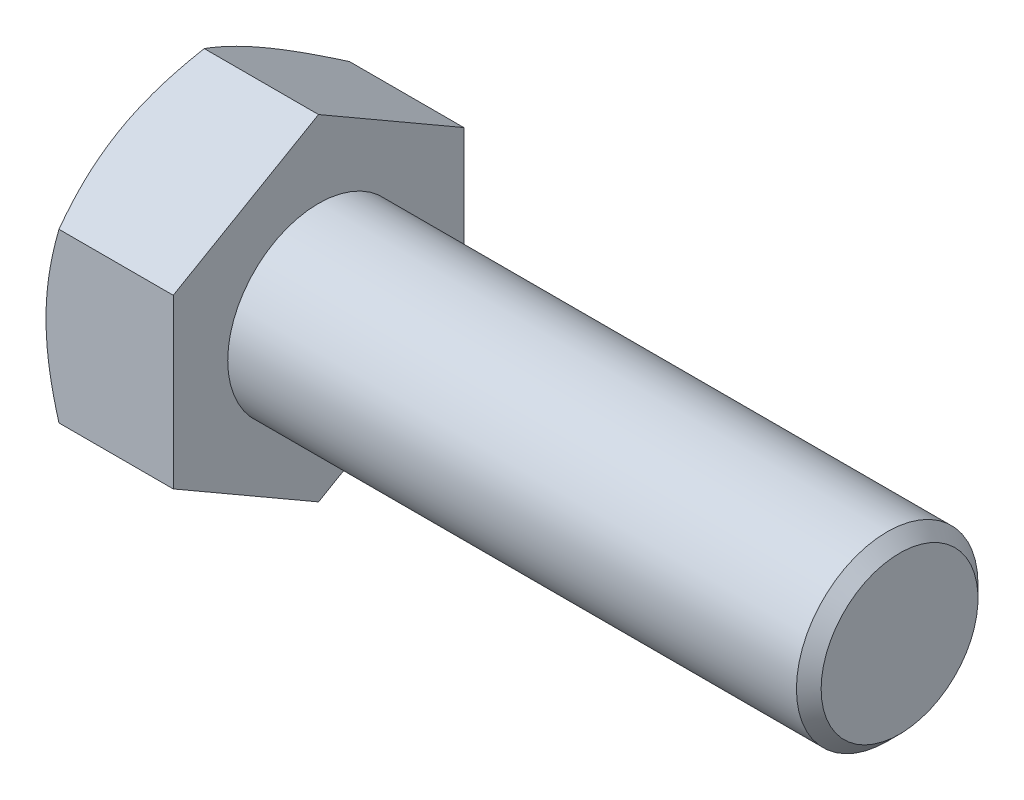
SolidWorks part; units mm, degrees
extrude "BaseHead" add sketch "Sketch1" along normal blind 22.2504
sketch "Sketch1" plane through (0, 0, 0) normal (1, 0, 0) x (0, 0, -1)
  line L0 (25.4, 14.6647) -> (25.4, -14.6647)
  line L1 (-25.4, 14.6647) -> (-25.4, -14.6647)
  line L2 (25.4, -14.6647) -> (0, -29.3294)
  line L3 (0, -29.3294) -> (-25.4, -14.6647)
  line L4 (25.4, 14.6647) -> (0, 29.3294)
  line L5 (0, 29.3294) -> (-25.4, 14.6647)
  dimension "D2" = 120
  dimension "D3" = 25.4
  dimension "D4" = 25.4
  dimension "D5" = 25.4
ref_plane "Plane1" through (0, 0, 0) normal (0, 0, 1) x (1, 0, 0)
ref_plane "Plane2" through (0, 0, 0) normal (0, 1, 0) x (1, 0, 0)
ref_plane "Plane3" through (0, 0, 0) normal (1, 0, 0) x (0, 0, -1)
sketch "BodySke" plane through (0, 0, 0) normal (0, 0, 1) x (1, 0, 0)
  line L0 (0, 14.6647) -> (0, -14.6647) construction
  line L1 (0, 0) -> (123.8504, 0)
  line L2 (0, 0) -> (0, 15.875)
  line L3 (0, 15.875) -> (121.6901, 15.875)
  line L4 (123.8504, 0) -> (123.8504, 13.7147)
  line L5 (22.2504, 29.3294) -> (22.2504, 14.6647) construction
  line L6 (123.8504, 13.7147) -> (121.6901, 15.875)
  line L7 (0, 0) -> (96.52, 0) construction
  line L8 (123.8504, -13.7147) -> (121.6901, -15.875) construction
  line L9 (0, -15.875) -> (121.6901, -15.875) construction
  line L10 (25.8801, 15.24) -> (25.8801, -3.81) construction
  line L11 (22.2504, 15.24) -> (22.2504, -3.81) construction
  line L12 (22.2504, 14.6647) -> (22.2504, -14.6647) construction
  dimension "Diameter" = 31.75
revolve "BaseBody" add sketch "BodySke" angle 360 about L7
cosmetic thread "ThreadCosmetic" [suppressed] parameters "Thread_length"=97.9703, "Thread_minor"=27.4295
sketch "Sketch3" plane through (0, 0, 0) normal (0, 0, 1) x (1, 0, 0)
  line L0 (0, 25.4) -> (5.9348, 35.6794)
  line L1 (0, 29.3294) -> (0, 14.6647) construction
  line L2 (5.9348, 35.6794) -> (5.9348, 42.0294)
  line L3 (5.9348, 42.0294) -> (-12.7, 42.0294)
  line L4 (-12.7, 42.0294) -> (-12.7, 25.4)
  line L5 (-12.7, 25.4) -> (0, 25.4)
  line L6 (0, 0) -> (99.06, 0) construction
  line L7 (22.2504, 29.3294) -> (0, 29.3294) construction
  dimension "D1" = 25.4
  dimension "D2" = 6.35
  dimension "D3" = 12.7
  dimension "D4" = 6.35
  dimension "Head_ch_ang" = 30
revolve "HeadChamfer" cut sketch "Sketch3" angle 360 about L6
fillet "HeadFillet" [suppressed] radius 2.286
sketch "ThdSchSke" plane through (0, 0, 0) normal (0, 0, 1) x (1, 0, 0)
  line L0 (25.8801, -13.7147) -> (24.3674, -15.875)
  line L1 (25.8801, -13.7147) -> (27.3927, -15.875)
  line L2 (27.3927, -15.875) -> (27.3927, -19.8438)
  line L3 (-3.175, 0) -> (5.1513, 0) construction
  line L5 (27.3927, -19.8438) -> (24.3674, -19.8438)
  line L6 (24.3674, -19.8438) -> (24.3674, -15.875)
  dimension "Thread_minor" = 27.4295
  dimension "Diameter" = 31.75
  dimension "Start" = 25.8801
revolve "ThreadSchematic" [suppressed] cut sketch "ThdSchSke" angle 360 about L3
pattern_linear "ThdSchPat" [suppressed]
equation "\"D3@Sketch1\" = \"Width_flats@Sketch1\" / 2"
equation "\"D4@Sketch1\" = \"D3@Sketch1\""
equation "\"D5@Sketch1\" = \"D4@Sketch1\""
equation "\"Thread_minor@ThreadCosmetic\" = \"Minor_dia@BodySke\""
equation "\"D1@Sketch3\" = \"Width_flats@Sketch1\" / 2"
equation "\"Thread_length@ThreadCosmetic\" = ((sgn( (\"Length@BodySke\" - \"Advance@BodySke\" ) - \"Thread_nom@BodySke\" )-1)*( (\"Length@BodySke\" - \"Advance@BodySke\" ) - \"Thread_nom@BodySke\" ))/-2+ \"Thread_nom@BodySke\""
equation "\"Thread_minor@ThdSchSke\" = \"Minor_dia@BodySke\""
equation "\"Diameter@ThdSchSke\" = \"Diameter@BodySke\""
equation "\"Overcut@ThdSchSke\" = \"Diameter@BodySke\" * 1.25"
equation "\"Start@ThdSchSke\" = \"Head_ht@BaseHead\" + \"Length@BodySke\" - \"Thread_length@ThreadCosmetic\"  '---Non-countersunk---"
equation "\"Num_threads@ThdSchPat\" = int( \"Thread_length@ThreadCosmetic\" / \"Advance@BodySke\" + 0.999 )  + 1"
equation "\"Advance@ThdSchPat\" = \"Thread_length@ThreadCosmetic\" /  (\"Num_threads@ThdSchPat\" - 1) 'relax it"
equation "\"Num_threads@ThdSchPat\" = \"Num_threads@ThdSchPat\" - sgn( \"Num_threads@ThdSchPat\" - 1) '---chamfered tips only---"
